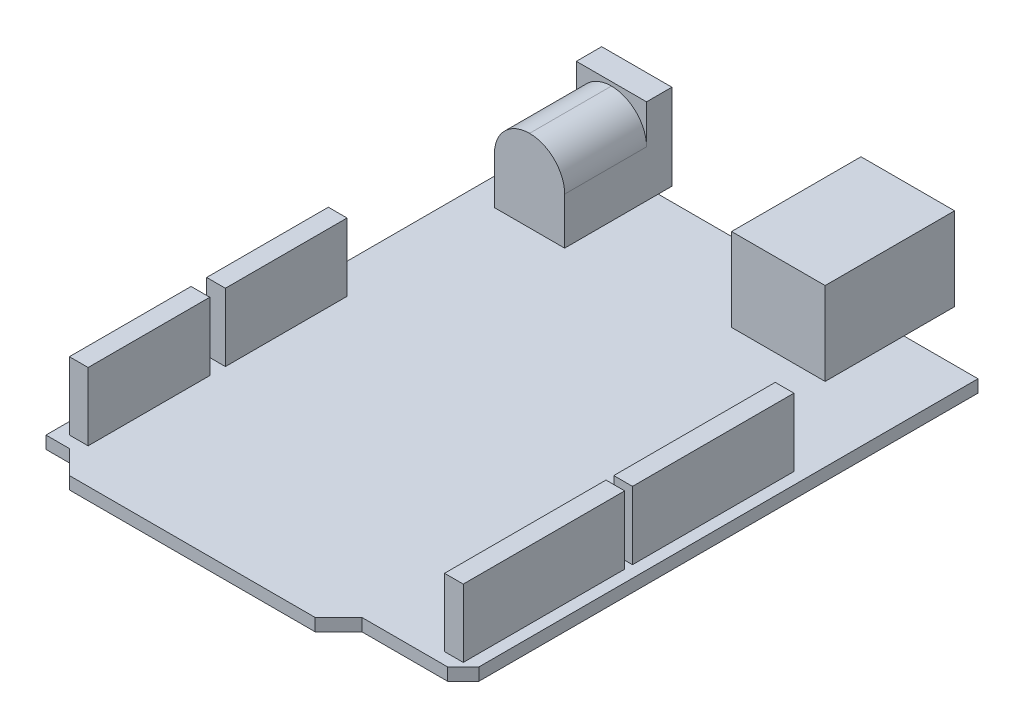
SolidWorks part; units mm, degrees
ref_plane "Front Plane" through (0, 0, 0) normal (0, 0, 1) x (1, 0, 0)
ref_plane "Top Plane" through (0, 0, 0) normal (0, 1, 0) x (1, 0, 0)
ref_plane "Right Plane" through (0, 0, 0) normal (1, 0, 0) x (0, 0, -1)
sketch "Sketch1" plane through (0, 0, 0) normal (0, 1, 0) x (1, 0, 0)
  line L0 (-26.75, -66) -> (-23.75, -66)
  line L1 (-26.75, 0) -> (26.75, 0)
  line L2 (-26.75, 0) -> (-26.75, -66)
  line L3 (-26.75, -66) -> (26.75, -66) construction
  line L4 (26.75, 0) -> (26.75, -66)
  line L5 (-23.75, -66) -> (-20.75, -69)
  line L6 (-20.75, -69) -> (10.75, -69)
  line L7 (10.75, -69) -> (13.75, -66)
  line L8 (13.75, -66) -> (26.75, -66)
  dimension "D1" = 53.5
  dimension "D2" = 66
  dimension "D3" = 3
  dimension "D4" = 3
  dimension "D5" = 37.5
extrude "Boss-Extrude1" add sketch "Sketch1" along normal blind 1.6
chamfer "Chamfer1" distance 2 angle 45 1 edges at (26.75, 0.8, 66)
sketch "Sketch2" plane through (0, 1.6, 0) normal (0, 1, 0) x (1, 0, 0)
  line L0 (26.75, -64) -> (26.75, 0) construction
  line L1 (17.25, 6.5) -> (5.25, 6.5)
  line L2 (17.25, 6.5) -> (17.25, -10.1)
  line L3 (17.25, -10.1) -> (5.25, -10.1)
  line L4 (5.25, 6.5) -> (5.25, -10.1)
  line L5 (26.75, 0) -> (-26.75, 0) construction
  dimension "D1" = 9.5
  dimension "D2" = 12
  dimension "D3" = 6.5
  dimension "D4" = 16.6
extrude "Boss-Extrude2" add sketch "Sketch2" along normal blind 10.65
sketch "Sketch3" plane through (0, 1.6, 0) normal (0, 1, 0) x (1, 0, 0)
  line L0 (-26.75, 0) -> (-26.75, -66) construction
  line L1 (-25.25, -64.5) -> (-22.85, -64.5)
  line L2 (-25.25, -64.5) -> (-25.25, -48.9)
  line L3 (-25.25, -48.9) -> (-22.85, -48.9)
  line L4 (-22.85, -64.5) -> (-22.85, -48.9)
  line L5 (-25.25, -46.9) -> (-22.85, -46.9)
  line L6 (-25.25, -46.9) -> (-25.25, -31.3)
  line L7 (-25.25, -31.3) -> (-22.85, -31.3)
  line L8 (-22.85, -46.9) -> (-22.85, -31.3)
  line L9 (25.25, -64.5) -> (22.85, -64.5)
  line L10 (25.25, -64.5) -> (25.25, -43.8)
  line L11 (25.25, -43.8) -> (22.85, -43.8)
  line L12 (22.85, -64.5) -> (22.85, -43.8)
  line L13 (25.25, -42.8) -> (22.85, -42.8)
  line L14 (25.25, -42.8) -> (25.25, -22.1)
  line L15 (25.25, -22.1) -> (22.85, -22.1)
  line L16 (22.85, -42.8) -> (22.85, -22.1)
  line L17 (26.75, -64) -> (26.75, 0) construction
  line L18 (-26.75, -66) -> (-23.75, -66) construction
  line L19 (13.75, -66) -> (24.75, -66) construction
  dimension "D1" = 2.4
  dimension "D2" = 1.5
  dimension "D3" = 1.5
  dimension "D4" = 1.5
  dimension "D5" = 2
  dimension "D6" = 15.6
  dimension "D7" = 1.5
  dimension "D8" = 20.7
  dimension "D9" = 1
  dimension "D10" = 20.7
extrude "Boss-Extrude3" add sketch "Sketch3" along normal blind 8.7
sketch "Sketch4" plane through (0, 0, 0) normal (0, 0, -1) x (-1, 0, 0)
  line L0 (-5.25, 1.6) -> (26.75, 1.6) construction
  line L1 (23.25, 12.6) -> (14.25, 12.6)
  line L2 (23.25, 12.6) -> (23.25, 1.6)
  line L3 (23.25, 1.6) -> (14.25, 1.6)
  line L4 (14.25, 12.6) -> (14.25, 1.6)
  line L5 (26.75, 1.6) -> (26.75, 0) construction
  dimension "D1" = 9
  dimension "D2" = 11
  dimension "D3" = 3.5
extrude "Boss-Extrude4" add sketch "Sketch4" along normal blind 1.75 and the other way blind 1.5
sketch "Sketch5" plane through (0, 0, 1.5) normal (0, 0, 1) x (1, 0, 0)
  line L0 (-14.25, 12.6) -> (-14.25, 1.6) construction
  line L1 (-23.25, 1.6) -> (-14.25, 1.6)
  line L2 (-23.25, 1.6) -> (-23.25, 12.1)
  line L3 (-23.25, 12.1) -> (-14.25, 12.1)
  line L4 (-14.25, 1.6) -> (-14.25, 12.1)
  dimension "D1" = 10.5
extrude "Boss-Extrude5" add sketch "Sketch5" along normal blind 10.5
fillet "Fillet1" radius 4.5 2 edges at (-14.25, 12.1, 6.75) (-23.25, 12.1, 6.75)
